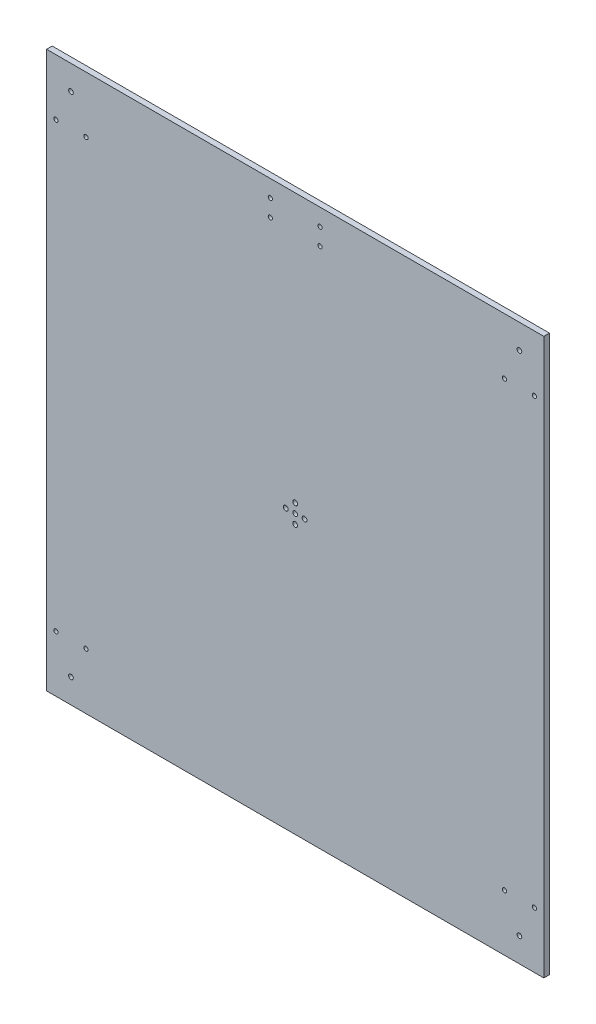
SolidWorks part; units mm, degrees
ref_plane "Спереди" through (0, 0, 0) normal (0, 0, 1) x (1, 0, 0)
ref_plane "Сверху" through (0, 0, 0) normal (0, 1, 0) x (1, 0, 0)
ref_plane "Справа" through (0, 0, 0) normal (1, 0, 0) x (0, 0, -1)
sketch "Эскиз3" plane through (0, 0, 0) normal (0, 0, 1) x (1, 0, 0)
  line L0 (0, 0) -> (0, 10) construction
  line L5 (265, -296.15) -> (-265, -296.15)
  line L6 (265, -296.15) -> (265, 296.15)
  line L7 (265, 296.15) -> (-265, 296.15)
  line L8 (-265, -296.15) -> (-265, 296.15)
  line L9 (0, 0) -> (10, 0) construction
  line L10 (0, 0) -> (0, -10) construction
  line L11 (0, 0) -> (-10, 0) construction
  circle A0 centre (0, 0) radius 2.55
  circle A1 centre (0, 10) radius 2.55
  circle A2 centre (10, 0) radius 2.55
  circle A3 centre (0, -10) radius 2.55
  circle A4 centre (-10, 0) radius 2.55
  point P0 (0, 0)
  point P5 (-265, 0)
  point P6 (0, 296.15)
  point P21 (0, 0)
  dimension "D3" = 5.1
  dimension "D4" = 5.1
  dimension "D1" = 592.3
  dimension "D2" = 530
  dimension "D5" = 10
  dimension "D6" = 4
extrude "Бобышка-Вытянуть1" add sketch "Эскиз3" along normal blind 6
sketch "Эскиз4" plane through (0, 0, 6) normal (0, 0, 1) x (1, 0, 0)
  line L0 (265, 296.15) -> (-265, 296.15) construction
  line L1 (-265, 296.15) -> (-265, -296.15) construction
  circle A0 centre (-239, 270.15) radius 2.5
  dimension "D1" = 5
  dimension "D2" = 26
  dimension "D3" = 26
extrude "Вырез-Вытянуть1" cut sketch "Эскиз4" against normal through all contours A0
pattern_linear "Линейный массив1" count 2 spacing 478 along (1, 0, 0) count 2 spacing 540.3 along (0, -1, 0) of "Вырез-Вытянуть1"
sketch "Эскиз7" plane through (0, 0, 0) normal (0, 0, -1) x (-1, 0, 0)
  line L9 (-26.5, 278.15) -> (26.5, 278.15) construction
  line L10 (-26.5, 278.15) -> (-26.5, 260.15) construction
  line L11 (-26.5, 260.15) -> (26.5, 260.15) construction
  line L16 (26.5, 278.15) -> (26.5, 260.15) construction
  line L17 (-265, 296.15) -> (265, 296.15) construction
  circle A0 centre (-26.5, 278.15) radius 2.25
  circle A1 centre (26.5, 278.15) radius 2.25
  circle A2 centre (-26.5, 260.15) radius 2.25
  circle A3 centre (26.5, 260.15) radius 2.25
  point P4 (0, 260.15)
  dimension "D4" = 4.5
  dimension "D5" = 4.5
  dimension "D6" = 4.5
  dimension "D7" = 4.5
  dimension "D1" = 53
  dimension "D2" = 18
  dimension "D3" = 18
extrude "Вырез-Вытянуть2" cut sketch "Эскиз7" against normal through all
sketch "Эскиз8" plane through (0, 0, 0) normal (0, 0, -1) x (-1, 0, 0)
  line L0 (223, 236.15) -> (255, 236.15) construction
  line L8 (265, 296.15) -> (265, -296.15) construction
  line L9 (-265, 296.15) -> (265, 296.15) construction
  circle A4 centre (223, 236.15) radius 2.25
  circle A5 centre (255, 236.15) radius 2.25
  dimension "D3" = 32
  dimension "D4" = 10
  dimension "D5" = 60
  dimension "D1" = 4.5
  dimension "D2" = 4.5
extrude "Вырез-Вытянуть3" cut sketch "Эскиз8" against normal through all
pattern_linear "Линейный массив2" count 2 spacing 472.3 along (0, -1, 0) count 2 spacing 478 along (1, 0, 0) of "Вырез-Вытянуть3"
equation "\"Ширина груза\"= 420"
equation "\"Глубина груза\"= 490"
equation "\"Высота груза\"= 297"
equation "\"Ширина ячейки\"= \"Ширина груза\" + 10"
equation "\"Глубина ячейки\"= \"Глубина груза\" + 10"
equation "\"Высота ячейки\"= \"Высота груза\" + 10 + 13"
equation "\"Колво ячеек ширина\"= 2"
equation "\"Колво ячеек высота\"= 2"
equation "\"Толщина стенки\" = \"Толщина тонких панелей\""
equation "\"Крепление дверцы\"= 5 "
equation "\"Ширина рейки\"= \"Толщина шестерни\""
equation "\"Высота рейки\"= 20"
equation "\"Высота пола\" = 2*\"Толщина тонких панелей\""
equation "\"Колво полозьев\"= 5"
equation "\"Отступ рейки\"= 20"
equation "\"Глубина каретки\"= \"Глубина ячейки\" + 30 + \"Мотор Y высота корпуса\" + 20"
equation "\"Длинна рейки\" = (\"Ширина ячейки\"+\"Толщина вертикальных стенок\"+\"Крепление дверцы\")*\"Колво ячеек ширина\"+\"Ширина ячейки выгрузки\"*\"Колво выгрузки\"+\"Толщина вертикальных стенок\"+2*\"Отступ крепления мотора фиксации\"-\"Крепление дверцы\"*\"Колво ячеек ширина\""
equation "\"Отступ шпильки\"= 26"
equation "\"Диаметр шпильки\"= 5"
equation "\"D1@Бобышка-Вытянуть1\" = \"Толщина стенки\""
equation "\"D1@Эскиз4\"= \"Диаметр шпильки\""
equation "\"D2@Эскиз4\"=\"Отступ шпильки\""
equation "\"D3@Эскиз4\"= \"Отступ шпильки\""
equation "\"D2@Эскиз3\"=\"Ширина ячейки\" + \"Ширина пластины\" * 2"
equation "\"D1@Эскиз3\"=\"Глубина каретки\" "
equation "\"D3@Линейный массив1\"=\"Ширина ячейки\"  +\"Ширина пластины\" *2 - \"Отступ шпильки\" * 2"
equation "\"D4@Линейный массив1\"=\"Глубина каретки\" + \"Ширина рейки\" * 2 - \"Отступ шпильки\" * 2 - \"Ширина рейки\" * 2"
equation "\"Длинна шпильки\" = (\"Высота ячейки\"+\"Толщина горизонтальных плит\"+\"Высота пола\")*\"Колво ячеек высота\"+2*(\"Толщина горизонтальных плит\"+\"Отступ рейки\")"
equation "\"Ширина пластины\"= 50  "
equation "\"Высота зона выгрузки\"= \"Высота ячейки\" * 2 + \"Толщина стенки\" * 2"
equation "\"Колво выгрузки\"= 1"
equation "\"Отступ крепления мотора фиксации\" = (\"Ширина пластины\"+20-\"Толщина вертикальных стенок\")/2"
equation "\"Мотор X ширина корпуса\"= 42.3"
equation "\"Мотор X высота корпуса\"= 42.3"
equation "\"Мотор X длина корпуса\"= 40"
equation "\"Мотор X вылет вала\"= 19.8"
equation "\"Мотор Y ширина корпуса\"= 42.3"
equation "\"Мотор Y высота корпуса\"= 42.3"
equation "\"Мотор Y длина корпуса\"= 48"
equation "\"Мотор Y вылет вала\"= 30"
equation "\"Мотор Z ширина корпуса\"= 42"
equation "\"Мотор Z высота корпуса\"= 42"
equation "\"Мотор Z длина корпуса\"= 40"
equation "\"Мотор Z вылет вала\"= 23"
equation "\"Мотор диаметр вала ПРЕДВ\"= 5"
equation "\"Мотор шаг крепления ПРЕДВ\"= 31"
equation "\"Мотор диаметр отверстий ПРЕДВ\"= 3"
equation "\"Мотор глубина отверстий ПРЕДВ\"= 4.5"
equation "\"Мотор диаметр буртика ПРЕДВ\"= 22"
equation "\"Мотор высота буртика ПРЕДВ\"= 2"
equation "\"Мотор диаметр шкива ПРЕДВ\"= 16"
equation "\"Мотор длина шкива ПРЕДВ\"= 12"
equation "\"Мотор отступ шкива ПРЕДВ\"= 5"
equation "\"Мотор X шаг градусов\"= 1.8"
equation "\"Мотор Y шаг градусов\"= 1.8"
equation "\"Мотор Z шаг градусов\"= 1.8"
equation "\"Мотор Y диаметр ротора\"= 25.78"
equation "\"Толщина шестерни\"= 10"
equation "\"Ширина ячейки выгрузки\" = \"Ширина ячейки\"+\"Толщина вертикальных стенок\"+2*\"Отступ крепления мотора фиксации\""
equation "\"D3@Линейный массив2\"=592.3-60*2"
equation "\"D4@Линейный массив2\"=530 - 26*2"
equation "\"Толщина тонких панелей\"= 6"
equation "\"Толщина вертикальных стенок\"= 18"
equation "\"Толщина горизонтальных плит\"= 18"
equation "\"Базовая высота корпуса\"= (\"Высота ячейки\"+\"Толщина тонких панелей\"+\"Высота пола\")*\"Колво ячеек высота\"+6*\"Толщина тонких панелей\"+\"Мотор X ширина корпуса\"+\"Мотор Y ширина корпуса\"+75"
equation "\"Высота корпуса\"= (\"Высота ячейки\"+\"Толщина горизонтальных плит\"+\"Высота пола\")*\"Колво ячеек высота\"+2*\"Толщина горизонтальных плит\"+4*\"Толщина тонких панелей\"+\"Мотор X ширина корпуса\"+\"Мотор Y ширина корпуса\"+75"
equation "\"Смещение центра корпуса\"= (\"Высота корпуса\"-\"Базовая высота корпуса\")/2-(\"Толщина горизонтальных плит\"-\"Толщина тонких панелей\")"
equation "\"Отметка пола\"= -\"Базовая высота корпуса\"/2+\"Толщина тонких панелей\""
equation "\"Отметка потолка\"= \"Отметка пола\"+\"Высота корпуса\"-2*\"Толщина горизонтальных плит\""
equation "\"Отметка верхней полки\"= \"Отметка потолка\"-(28+\"Толщина тонких панелей\")-\"Высота ячейки\"-\"Высота пола\""
equation "\"Отметка нижней полки\"= \"Отметка верхней полки\"-\"Высота ячейки\"-\"Высота пола\"-\"Толщина горизонтальных плит\""
